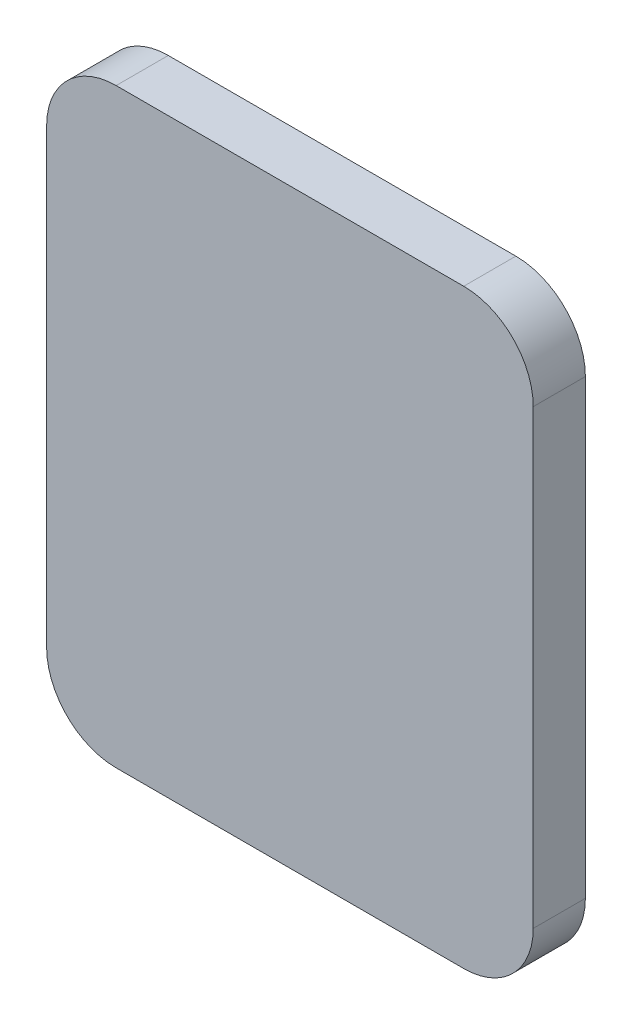
SolidWorks part; units mm, degrees
ref_plane "Front Plane" through (0, 0, 0) normal (0, 0, 1) x (1, 0, 0)
ref_plane "Top Plane" through (0, 0, 0) normal (0, 1, 0) x (1, 0, 0)
ref_plane "Right Plane" through (0, 0, 0) normal (1, 0, 0) x (0, 0, -1)
sketch "Sketch1" plane through (0, 0, 0) normal (0, 0, 1) x (1, 0, 0)
  line L1 (-62.5, 125.5) -> (77.5, 125.5)
  line L2 (-62.5, 125.5) -> (-62.5, -44.5)
  line L3 (-62.5, -44.5) -> (77.5, -44.5)
  line L4 (77.5, 125.5) -> (77.5, -44.5)
  line L5 (-62.5, 125.5) -> (77.5, -44.5) construction
  line L6 (-62.5, -44.5) -> (77.5, 125.5) construction
  line L7 (7.53, -26.518) -> (7.47, -26.518) construction
  line L8 (7.47, -26.3909) -> (7.47, -26.6452) construction
  line L9 (7.53, -26.6452) -> (7.53, -26.3909) construction
  line L10 (7.5, -26.518) -> (7.5, 40.5) construction
  line L12 (58.5, -26.5) -> (-0.5, -26.5) construction
  line L16 (7.47, -26.3909) -> (7.47, -26.6452) construction
  line L17 (7.53, -26.6452) -> (7.53, -26.3909) construction
  point P0 (7.5, 40.5)
  point P5 (7.5, 43.7691)
  dimension "D1" = 170
  dimension "D2" = 140
  dimension "D3" = 18
extrude "Boss-Extrude1" add sketch "Sketch1" along normal blind 5 and the other way blind 10
fillet "Fillet1" radius 20 4 edges at (-62.5, 125.5, -2.5) (77.5, 125.5, -2.5) (77.5, -44.5, -2.5) (-62.5, -44.5, -2.5)
shell "Shell2" thickness 4 removed face at (7.5, 40.5, -10)
sketch "Sketch2" plane through (0, 0, 0) normal (0, 0, -1) x (-1, 0, 0)
  arc A0 (0, 1.35) -> (0, -1.35) centre (0, 0) ccw construction
  arc A1 (0, 1.35) -> (0, -1.35) centre (0, 0) ccw construction
  arc A2 (0, -21.65) -> (0, -24.35) centre (0, -23) ccw construction
  arc A3 (0, -21.65) -> (0, -24.35) centre (0, -23) ccw construction
  arc A4 (-58, -21.65) -> (-58, -24.35) centre (-58, -23) ccw construction
  arc A5 (-58, -21.65) -> (-58, -24.35) centre (-58, -23) ccw construction
  arc A6 (-58, 1.35) -> (-58, -1.35) centre (-58, 0) ccw construction
  arc A7 (-58, 1.35) -> (-58, -1.35) centre (-58, 0) ccw construction
  circle A8 centre (0, -23) radius 2.1
  circle A9 centre (0, 0) radius 2.1
  circle A10 centre (-58, 0) radius 2.1
  circle A11 centre (-58, -23) radius 2.1
  dimension "D1" = 4.2
extrude "Cut-Extrude1" cut sketch "Sketch2" against normal blind 4.5
